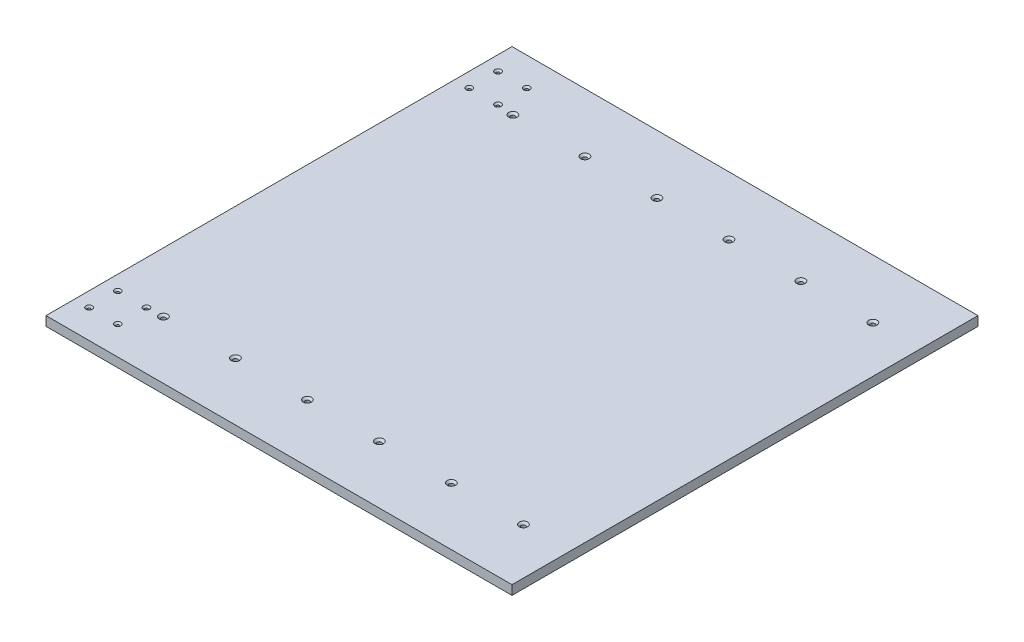
SolidWorks part; units mm, degrees
material "Buk"
ref_plane "Płaszczyzna przednia" through (0, 0, 0) normal (0, 0, 1) x (1, 0, 0)
ref_plane "Płaszczyzna górna" through (0, 0, 0) normal (0, 1, 0) x (1, 0, 0)
ref_plane "Płaszczyzna prawa" through (0, 0, 0) normal (1, 0, 0) x (0, 0, -1)
sketch "Szkic1" plane through (0, 0, 0) normal (0, 1, 0) x (1, 0, 0)
  line L1 (0, 0) -> (500, 0)
  line L2 (0, 0) -> (0, 500)
  line L3 (0, 500) -> (500, 500)
  line L4 (500, 0) -> (500, 500)
  dimension "D1" = 500
extrude "Dodanie-wyciągnięcie1" add sketch "Szkic1" along normal blind 10
sketch "Szkic2" plane through (0, 10, 0) normal (0, 1, 0) x (1, 0, 0)
  line L0 (0, 0) -> (500, 0) construction
  line L1 (0, 500) -> (0, 0) construction
  line L2 (0, 250) -> (500, 250) construction
  line L3 (500, 0) -> (500, 500) construction
  circle A0 centre (15.6, 30.6) radius 1.6
  circle A1 centre (15.6, 61.4) radius 1.6
  circle A2 centre (46.4, 61.4) radius 1.6
  circle A3 centre (46.4, 30.6) radius 1.6
  circle A4 centre (15.6, 438.6) radius 1.6
  circle A5 centre (15.6, 469.4) radius 1.6
  circle A6 centre (46.4, 469.4) radius 1.6
  circle A7 centre (46.4, 438.6) radius 1.6
  dimension "D1" = 3.2
  dimension "D2" = 3.2
  dimension "D3" = 3.2
  dimension "D4" = 3.2
  dimension "D5" = 30.6
  dimension "D6" = 30.6
  dimension "D7" = 30.8
  dimension "D8" = 15.6
  dimension "D9" = 15.6
  dimension "D10" = 30.8
  dimension "D11" = 30.8
  dimension "D12" = 30.8
hole_wizard "Pogłębienie stożkowe pod M3 Wkręt ustalający1" positions "Szkic3" profile "Szkic5" countersink size "M3" standard "Ansi Metric"
sketch "Szkic3" plane through (0, 10, 0) normal (0, 1, 0) x (1, 0, 0)
  point P0 (46.4, 30.6)
  point P3 (46.4, 61.4)
  point P6 (15.6, 61.4)
  point P9 (15.6, 30.6)
  point P12 (46.4, 438.6)
  point P15 (46.4, 469.4)
  point P18 (15.6, 469.4)
  point P21 (15.6, 438.6)
sketch "Szkic5" plane through (46.4, 10, -30.6) normal (1, 0, 0) x (0, 0, 1)
  line L0 (0, 0) -> (0, 11.0215)
  line L1 (0, 11.0215) -> (1.7, 10)
  line L2 (1.7, 10) -> (1.7, 1.66)
  line L3 (1.7, 1.66) -> (3.36, 0)
  line L5 (3.36, 0) -> (0, 0)
  line L6 (-1.7, 1.66) -> (-3.36, 0) construction
  line L10 (0, 11.0215) -> (-1.7, 10) construction
  line L11 (0, -6.35) -> (0, 107.95) construction
  dimension "Œrednica otworu" = 3.4
  dimension "G³êbokoœc otworu" = 10
  dimension "Œrednica zewnêtrznego pog³êbienia sto¿kowego" = 6.72
  dimension "K¹t zewnêtrznego pog³êbienia sto¿kowego" = 90
  dimension "K¹t wiert³a" = 118
hole_wizard "Pogłębienie stożkowe pod M4 Wkręt ustalający1" positions "Szkic6" profile "Szkic7" countersink size "M4" standard "Ansi Metric"
sketch "Szkic6" plane through (0, 10, 0) normal (0, 1, 0) x (1, 0, 0)
  line L0 (0, 500) -> (0, 0) construction
  line L1 (0, 0) -> (500, 0) construction
  point P0 (63.9, 62.07)
  point P14 (141.15, 62.07)
  point P15 (218.4, 62.07)
  point P16 (295.65, 62.07)
  point P17 (372.9, 62.07)
  point P18 (450.15, 62.07)
  point P19 (141.15, 437.07)
  point P20 (218.4, 437.07)
  point P21 (295.65, 437.07)
  point P22 (372.9, 437.07)
  point P23 (450.15, 437.07)
  point P24 (63.9, 437.07)
  dimension "D1" = 63.9
  dimension "D2" = 62.07
  dimension "D3" = 6
  dimension "D4" = 2
sketch "Szkic7" plane through (63.9, 10, -62.07) normal (1, 0, 0) x (0, 0, 1)
  line L0 (0, 0) -> (0, 12.9421)
  line L1 (0, 12.9421) -> (2.4, 11.5)
  line L2 (2.4, 11.5) -> (2.4, 2.08)
  line L3 (2.4, 2.08) -> (4.48, 0)
  line L5 (4.48, 0) -> (0, 0)
  line L6 (-2.4, 2.08) -> (-4.48, 0) construction
  line L10 (0, 12.9421) -> (-2.4, 11.5) construction
  line L11 (0, -6.35) -> (0, 107.95) construction
  dimension "Œrednica otworu" = 4.8
  dimension "G³êbokoœc otworu" = 11.5
  dimension "Œrednica zewnêtrznego pog³êbienia sto¿kowego" = 8.96
  dimension "K¹t zewnêtrznego pog³êbienia sto¿kowego" = 90
  dimension "K¹t wiert³a" = 118
sketch "Szkic8" plane through (0, 0, 0) normal (0, -1, 0) x (1, 0, 0)
  line L0 (0, -500) -> (0, 0) construction
  line L1 (60, -37) -> (460, -37)
  line L2 (60, -37) -> (60, -47)
  line L3 (60, -47) -> (460, -47)
  line L4 (460, -37) -> (460, -47)
  line L5 (0, 0) -> (500, 0) construction
  line L6 (60, -77) -> (60, -87)
  line L7 (60, -77) -> (460, -77)
  line L8 (460, -77) -> (460, -87)
  line L9 (60, -87) -> (460, -87)
  line L10 (60, -452) -> (60, -462)
  line L11 (60, -462) -> (460, -462)
  line L12 (460, -452) -> (460, -462)
  line L13 (60, -452) -> (460, -452)
  line L14 (60, -412) -> (60, -422)
  line L15 (60, -412) -> (460, -412)
  line L16 (460, -412) -> (460, -422)
  line L17 (60, -422) -> (460, -422)
  dimension "D1" = 10
  dimension "D2" = 400
  dimension "D3" = 60
  dimension "D4" = 2
  dimension "37" = 37
  dimension "D5" = 10
  dimension "D6" = 375
extrude "Wytnij-wyciągnięcie1" cut sketch "Szkic8" against normal blind 1
fillet "Zaokrąglenie1" radius 2 16 edges at (460, 1, -457) (260, 1, -462) (60, 1, -457) (260, 1, -452) (460, 1, -417) (260, 1, -422) (60, 1, -417) (260, 1, -412) (460, 1, -82) (260, 1, -87) (60, 1, -82) (260, 1, -77) (260, 1, -37) (460, 1, -42) (260, 1, -47) (60, 1, -42)
sketch "Sketch1" plane through (0, 0, 0) normal (0, -1, 0) x (1, 0, 0)
  line L0 (0, 0) -> (500, 0) construction
  line L1 (500, 0) -> (500, -500) construction
  line L2 (500, -500) -> (0, -500) construction
  circle A0 centre (468, -46) radius 5
  circle A1 centre (468, -454) radius 5
  dimension "D1" = 46
  dimension "D2" = 10
  dimension "D3" = 32
  dimension "D5" = 10
  dimension "D6" = 32
  dimension "D4" = 46
extrude "Cut-Extrude1" cut sketch "Sketch1" against normal blind 4
